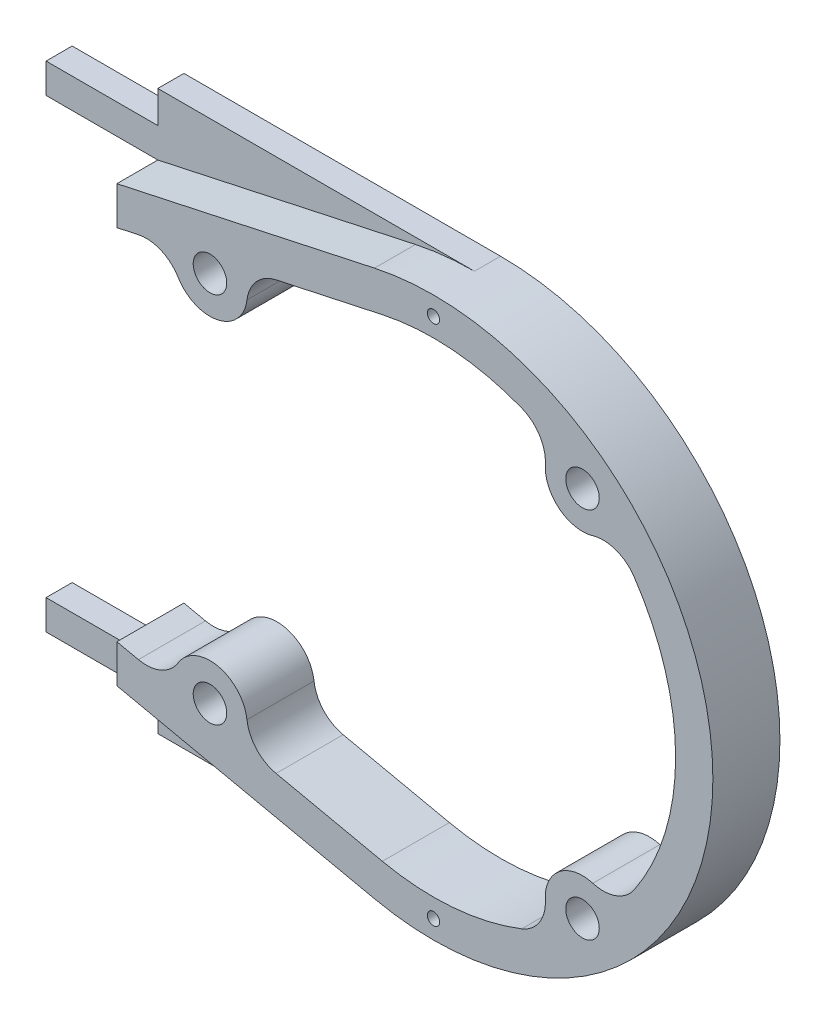
SolidWorks part; units mm, degrees
ref_plane "Front" through (0, 0, 0) normal (0, 0, 1) x (1, 0, 0)
ref_plane "Top" through (0, 0, 0) normal (0, 1, 0) x (1, 0, 0)
ref_plane "Right" through (0, 0, 0) normal (1, 0, 0) x (0, 0, -1)
sketch "Sketch1" plane through (47.5, -47.5, 0) normal (0, 0, 1) x (0, -1, 0)
  line L0 (-15.5701, -207.5) -> (1.8871, -126.7029)
  line L1 (-111.0339, -61.2273) -> (-104.8697, -89.757)
  line L2 (-79.4299, -207.5) -> (-15.5701, -207.5)
  line L3 (-96.8871, -126.7029) -> (-79.4299, -207.5)
  line L4 (-111.0339, -61.2273) -> (-79.4299, -207.5) construction
  line L5 (9.8697, -89.757) -> (16.0339, -61.2273)
  line L6 (-120.8084, -63.3392) -> (-89.2043, -209.6119)
  line L7 (-79.4299, -217.5) -> (-15.5701, -217.5)
  line L8 (-5.7957, -209.6119) -> (25.8084, -63.3392)
  line L9 (-15.5701, -207.5) -> (16.0339, -61.2273) construction
  line L10 (-97.5, -107.5) -> (-97.5, -7.5) construction
  line L11 (2.5, -107.5) -> (2.5, -7.5) construction
  line L12 (2.5, -7.5) -> (-97.5, -7.5) construction
  line L13 (-47.5, -47.5) -> (-47.5, -323.5722) construction
  line L14 (43.5196, -47.5) -> (-142.3518, -47.5) construction
  arc A0 (-108.033, -23.8196) -> (-111.0339, -61.2273) centre (-47.5, -47.5) ccw
  arc A1 (16.0339, -61.2273) -> (-111.0339, -61.2273) centre (-47.5, -47.5) ccw construction
  arc A2 (-11.1095, 6.3584) -> (-83.8905, 6.3584) centre (-47.5, -47.5) ccw
  arc A3 (16.0339, -61.2273) -> (13.033, -23.8196) centre (-47.5, -47.5) ccw
  arc A4 (-79.4299, -207.5) -> (-79.4299, -207.5) centre (-79.4299, -207.5) ccw
  arc A5 (-15.5701, -207.5) -> (-15.5701, -207.5) centre (-15.5701, -207.5) ccw
  arc A6 (-89.2043, -209.6119) -> (-79.4299, -217.5) centre (-79.4299, -207.5) ccw
  arc A7 (-15.5701, -217.5) -> (-5.7957, -209.6119) centre (-15.5701, -207.5) ccw
  arc A8 (25.8084, -63.3392) -> (-120.8084, -63.3392) centre (-47.5, -47.5) ccw
  arc A9 (-92.3063, -116.0455) -> (-96.2976, -97.5725) centre (-97.5, -107.5) ccw
  circle A10 centre (-97.5, -107.5) radius 4.5
  circle A11 centre (2.5, -107.5) radius 4.5
  circle A12 centre (2.5, -7.5) radius 4.5
  circle A13 centre (-97.5, -7.5) radius 4.5
  arc A14 (-98.1101, -17.4814) -> (-87.896, -4.7138) centre (-97.5, -7.5) ccw
  arc A15 (-7.104, -4.7138) -> (3.1101, -17.4814) centre (2.5, -7.5) ccw
  arc A16 (1.2976, -97.5725) -> (-2.6937, -116.0455) centre (2.5, -107.5) ccw
  arc A17 (1.8871, -126.7029) -> (-2.6937, -116.0455) centre (-7.8873, -124.591) ccw
  arc A18 (9.8697, -89.757) -> (1.2976, -97.5725) centre (0.0953, -87.6451) cw
  arc A19 (3.1101, -17.4814) -> (13.033, -23.8196) centre (3.7202, -27.4627) cw
  arc A20 (-7.104, -4.7138) -> (-11.1095, 6.3584) centre (-16.708, -1.9275) ccw
  arc A21 (-87.896, -4.7138) -> (-83.8905, 6.3584) centre (-78.292, -1.9275) cw
  arc A22 (-98.1101, -17.4814) -> (-108.033, -23.8196) centre (-98.7202, -27.4627) ccw
  arc A23 (-104.8697, -89.757) -> (-96.2976, -97.5725) centre (-95.0953, -87.6451) ccw
  arc A24 (-92.3063, -116.0455) -> (-96.8871, -126.7029) centre (-87.1127, -124.591) ccw
  circle A26 centre (-117.5, -47.5) radius 1.65
  circle A27 centre (22.5, -47.5) radius 1.65
  point P22 (-47.5, -47.5)
  dimension "D2" = 75
  dimension "D7" = 9
  dimension "D8" = 9
  dimension "D9" = 9
  dimension "D10" = 9
  dimension "D16" = 10
  dimension "D17" = 10
  dimension "D18" = 10
  dimension "D19" = 10
  dimension "D20" = 10
  dimension "D21" = 3.3
  dimension "D22" = 3.3
  dimension "D24" = 70
  dimension "D3" = 50
  dimension "D4" = 50
  dimension "D5" = 40
  dimension "D6" = 100
  dimension "D11" = 100
  dimension "D12" = 160
  dimension "D13" = 63.8597
  dimension "D14" = 12.192
  dimension "D15" = 12.192
  dimension "D23" = 70
  dimension "D1" = 10
extrude "Boss-Extrude1" add sketch "Sketch1" along normal blind 18
sketch "Sketch3" plane through (0, 0, 0) normal (0, 0, -1) x (-1, 0, 0)
  line L0 (0, 0) -> (261.4966, 0) construction
  line L2 (265, 75) -> (0, 75)
  line L3 (275, 65) -> (275, -65)
  line L4 (265, -75) -> (0, -75)
  line L5 (0, 75) -> (0, -75)
  line L6 (275, 75) -> (0, -75) construction
  line L7 (275, -75) -> (0, 75) construction
  line L9 (170, 31.9299) -> (170, -31.9299) construction
  arc A0 (265, -75) -> (275, -65) centre (265, -65) ccw
  arc A1 (275, 65) -> (265, 75) centre (265, 65) ccw
  point P3 (137.5, 0)
  point P18 (0, 70)
  dimension "D3" = 10
  dimension "D1" = 75
  dimension "D2" = 105
extrude "Boss-Extrude2" add sketch "Sketch3" against normal blind 7
sketch "Sketch4" plane through (0, 0, 7) normal (0, 0, 1) x (1, 0, 0)
  line L0 (0, 0) -> (-275, 0) construction
  line L1 (-275, -65) -> (-275, 65) construction
  line L2 (0, -11) -> (-275, -11) construction
  line L3 (0, 66.4999) -> (0, -66.4999) construction
  line L4 (0, 11) -> (-275, 11) construction
  line L5 (0, -33) -> (-275, -33) construction
  line L6 (0, 33) -> (-275, 33) construction
  line L7 (-88.9755, -55) -> (-260.4482, -55) construction
  line L8 (0, 55) -> (-275, 55) construction
  line L9 (0, 66.4999) -> (0, -66.4999) construction
  line L10 (-266, 75) -> (-266, -75) construction
  line L11 (-265, 75) -> (0, 75) construction
  line L12 (0, -75) -> (-265, -75) construction
  line L13 (-183, 75) -> (-183, -75) construction
  circle A0 centre (-266, 55) radius 1.2
  circle A1 centre (-266, 33) radius 1.2
  circle A2 centre (-266, 11) radius 1.2
  circle A3 centre (-266, -11) radius 1.2
  circle A4 centre (-266, -33) radius 1.2
  circle A5 centre (-266, -55) radius 1.2
  circle A6 centre (-183, 55) radius 1.2
  circle A7 centre (-183, 33) radius 1.2
  circle A8 centre (-183, 11) radius 1.2
  circle A9 centre (-183, -11) radius 1.2
  circle A10 centre (-183, -33) radius 1.2
  circle A11 centre (-183, -55) radius 1.2
  dimension "D8" = 2.4
  dimension "D9" = 2.4
  dimension "D10" = 2.4
  dimension "D11" = 2.4
  dimension "D12" = 2.4
  dimension "D13" = 2.4
  dimension "D14" = 83
  dimension "D15" = 2.4
  dimension "D16" = 2.4
  dimension "D17" = 2.4
  dimension "D18" = 2.4
  dimension "D19" = 2.4
  dimension "D20" = 2.4
  dimension "D1" = 11
  dimension "D2" = 11
  dimension "D3" = 22
  dimension "D4" = 22
  dimension "D5" = 22
  dimension "D6" = 22
  dimension "D7" = 9
extrude "Cut-Extrude1" cut sketch "Sketch4" against normal through all
sketch "Sketch5" plane through (0, 0, 7) normal (0, 0, 1) x (1, 0, 0)
  line L6 (-42.257, -57.3697) -> (-13.7273, -63.5339)
  line L7 (0, -65) -> (0, 65)
  line L8 (-13.7273, 63.5339) -> (-42.257, 57.3697)
  line L9 (-79.2029, 49.3871) -> (-160, 31.9299)
  line L10 (-160, 31.9299) -> (-160, -31.9299)
  line L11 (-160, -31.9299) -> (-79.2029, -49.3871)
  line L12 (-42.257, -57.3697) -> (-13.7273, -63.5339)
  line L14 (-13.7273, 63.5339) -> (-42.257, 57.3697)
  line L15 (-79.2029, 49.3871) -> (-160, 31.9299)
  line L16 (-160, 31.9299) -> (-160, -31.9299)
  line L17 (-160, -31.9299) -> (-79.2029, -49.3871)
  line L18 (0, -65) -> (0, 65)
  circle A0 centre (-60, 50) radius 4.5 construction
  circle A1 centre (-60, -50) radius 4.5 construction
  circle A2 centre (-60, 50) radius 4.5
  circle A3 centre (-60, -50) radius 4.5
  arc A6 (-50.0725, -48.7976) -> (-42.257, -57.3697) centre (-40.1451, -47.5953) ccw
  arc A7 (-42.257, 57.3697) -> (-50.0725, 48.7976) centre (-40.1451, 47.5953) ccw
  arc A8 (-68.5455, 44.8063) -> (-50.0725, 48.7976) centre (-60, 50) ccw
  arc A9 (-68.5455, 44.8063) -> (-79.2029, 49.3871) centre (-77.091, 39.6127) ccw
  arc A10 (-79.2029, -49.3871) -> (-68.5455, -44.8063) centre (-77.091, -39.6127) ccw
  arc A11 (-50.0725, -48.7976) -> (-68.5455, -44.8063) centre (-60, -50) ccw
  arc A12 (-50.0725, -48.7976) -> (-42.257, -57.3697) centre (-40.1451, -47.5953) ccw
  arc A13 (-42.257, 57.3697) -> (-50.0725, 48.7976) centre (-40.1451, 47.5953) ccw
  arc A14 (-68.5455, 44.8063) -> (-50.0725, 48.7976) centre (-60, 50) ccw
  arc A15 (-68.5455, 44.8063) -> (-79.2029, 49.3871) centre (-77.091, 39.6127) ccw
  arc A16 (-79.2029, -49.3871) -> (-68.5455, -44.8063) centre (-77.091, -39.6127) ccw
  arc A17 (-50.0725, -48.7976) -> (-68.5455, -44.8063) centre (-60, -50) ccw
  arc A24 (-13.7273, -63.5339) -> (0, -65) centre (0, 0) ccw
  arc A25 (-13.7273, -63.5339) -> (0, -65) centre (0, 0) ccw
  arc A26 (0, 65) -> (-13.7273, 63.5339) centre (0, 0) ccw
  arc A27 (0, 65) -> (-13.7273, 63.5339) centre (0, 0) ccw
  dimension "D1" = 0
extrude "Cut-Extrude2" cut sketch "Sketch5" against normal through all
sketch "Sketch6" plane through (0, 0, 7) normal (0, 0, 1) x (1, 0, 0)
  line L0 (0, -75) -> (-265, -75) construction
  line L1 (-222.5, 75) -> (-222.5, -75) construction
  line L2 (-275, 0) -> (-170, 0) construction
  line L4 (-265, 71) -> (-180, 71)
  line L5 (-271, 65) -> (-271, -65)
  line L6 (-162.1119, 41.7043) -> (-15.8392, 73.3084)
  line L7 (0, 75) -> (-265, 75)
  line L8 (-275, 65) -> (-275, -65)
  line L9 (-265, -75) -> (0, -75)
  line L10 (-15.8392, -73.3084) -> (-162.1119, -41.7043)
  line L11 (-170, -31.9299) -> (-170, 31.9299)
  line L13 (-180, 75) -> (-265, 75)
  line L14 (-275, 65) -> (-275, -65)
  line L15 (-265, -75) -> (-180, -75)
  line L17 (-170, -65) -> (-170, 65)
  line L18 (-265, -71) -> (-180, -71)
  line L19 (-174, 65) -> (-174, -65)
  line L20 (-271, 71) -> (-174, -71) construction
  line L21 (-271, -71) -> (-174, 71) construction
  arc A0 (-180, -75) -> (-170, -65) centre (-180, -65) ccw
  arc A1 (-170, 65) -> (-180, 75) centre (-180, 65) ccw
  arc A2 (-180, 71) -> (-174, 65) centre (-180, 65) cw
  arc A3 (-174, -65) -> (-180, -71) centre (-180, -65) cw
  arc A4 (-162.1119, 41.7043) -> (-170, 31.9299) centre (-160, 31.9299) ccw
  arc A5 (-265, 75) -> (-275, 65) centre (-265, 65) ccw
  arc A6 (-275, -65) -> (-265, -75) centre (-265, -65) ccw
  arc A7 (-170, -31.9299) -> (-162.1119, -41.7043) centre (-160, -31.9299) ccw
  arc A9 (-265, 75) -> (-275, 65) centre (-265, 65) ccw
  arc A10 (-275, -65) -> (-265, -75) centre (-265, -65) ccw
  arc A12 (-265, -71) -> (-271, -65) centre (-265, -65) cw
  arc A13 (-265, 71) -> (-271, 65) centre (-265, 65) ccw
  arc A20 (-15.8392, -73.3084) -> (0, -75) centre (0, 0) ccw
  arc A22 (0, 75) -> (-15.8392, 73.3084) centre (0, 0) ccw
  point P21 (-170, -75)
  point P27 (-222.5, 0)
  dimension "D2" = 10
  dimension "D7" = 6
  dimension "D3" = 4
  dimension "D4" = 4
  dimension "D5" = 4
  dimension "D6" = 4
  dimension "D1" = 0
extrude "Boss-Extrude3" add sketch "Sketch6" along normal blind 92
sketch "Sketch7" plane through (-170, 0, 0) normal (1, 0, 0) x (0, 0, -1)
  line L0 (-18, 31.9299) -> (-18, -31.9299) construction
  line L1 (0, 0) -> (-140.0795, 0) construction
  circle A0 centre (-78, 48) radius 15
  circle A1 centre (-78, -48) radius 15
  dimension "D1" = 30
  dimension "D3" = 48
  dimension "D2" = 60
  dimension "D4" = 48
extrude "Cut-Extrude3" cut sketch "Sketch7" against normal up to next
sketch "Sketch8" plane through (0, -75, 0) normal (0, -1, 0) x (1, 0, 0)
  line L1 (-265, 99) -> (-180, 99) construction
  line L2 (-201.547, 79) -> (-275, 79)
  line L3 (-275, 99) -> (-275, 0) construction
  line L4 (-275, 79) -> (-275, 99)
  line L5 (-275, 99) -> (-190, 99)
  line L8 (-201.547, 79) -> (-190, 99)
  line L9 (-170, 99) -> (-170, 7) construction
  dimension "D1" = 60
  dimension "D2" = 20
  dimension "D3" = 20
  dimension "D4" = 85
extrude "Cut-Extrude4" cut sketch "Sketch8" against normal through all
sketch "Sketch10" plane through (0, 0, 0) normal (0, 1, 0) x (1, 0, 0)
  line L0 (-257, -64) -> (-257, -19) construction
  line L1 (-259.5, -64) -> (-259.5, -19)
  line L2 (-254.5, -64) -> (-254.5, -19)
  line L3 (-265, -79) -> (-265, 0) construction
  line L4 (-265, -79) -> (-201.547, -79) construction
  line L5 (-244, -64) -> (-244, -19) construction
  line L6 (-246.5, -64) -> (-246.5, -19)
  line L7 (-241.5, -64) -> (-241.5, -19)
  line L8 (-231, -64) -> (-231, -19) construction
  line L9 (-233.5, -64) -> (-233.5, -19)
  line L10 (-228.5, -64) -> (-228.5, -19)
  line L11 (-218, -64) -> (-218, -19) construction
  line L12 (-220.5, -64) -> (-220.5, -19)
  line L13 (-215.5, -64) -> (-215.5, -19)
  line L14 (-205, -64) -> (-205, -19) construction
  line L15 (-207.5, -64) -> (-207.5, -19)
  line L16 (-202.5, -64) -> (-202.5, -19)
  line L17 (-192, -64) -> (-192, -19) construction
  line L18 (-194.5, -64) -> (-194.5, -19)
  line L19 (-189.5, -64) -> (-189.5, -19)
  arc A0 (-259.5, -64) -> (-254.5, -64) centre (-257, -64) ccw
  arc A1 (-254.5, -19) -> (-259.5, -19) centre (-257, -19) ccw
  arc A2 (-246.5, -64) -> (-241.5, -64) centre (-244, -64) ccw
  arc A3 (-241.5, -19) -> (-246.5, -19) centre (-244, -19) ccw
  arc A4 (-233.5, -64) -> (-228.5, -64) centre (-231, -64) ccw
  arc A5 (-228.5, -19) -> (-233.5, -19) centre (-231, -19) ccw
  arc A6 (-220.5, -64) -> (-215.5, -64) centre (-218, -64) ccw
  arc A7 (-215.5, -19) -> (-220.5, -19) centre (-218, -19) ccw
  arc A8 (-207.5, -64) -> (-202.5, -64) centre (-205, -64) ccw
  arc A9 (-202.5, -19) -> (-207.5, -19) centre (-205, -19) ccw
  arc A10 (-194.5, -64) -> (-189.5, -64) centre (-192, -64) ccw
  arc A11 (-189.5, -19) -> (-194.5, -19) centre (-192, -19) ccw
  point P2 (-257, -41.5)
  point P15 (-244, -41.5)
  point P22 (-231, -41.5)
  point P29 (-218, -41.5)
  point P36 (-205, -41.5)
  point P43 (-192, -41.5)
  dimension "D4" = 15
  dimension "D1" = 45
  dimension "D2" = 8
  dimension "D3" = 5
  dimension "D5" = 6
extrude "Cut-Extrude6" cut sketch "Sketch10" against normal through all both and the other way through all
sketch "Sketch11" plane through (0, 0, 18) normal (0, 0, 1) x (1, 0, 0)
  line L0 (-162.1119, 41.7043) -> (-170, 41.7043)
  line L1 (-170, 31.9299) -> (-170, 65) construction
  line L2 (-170, 41.7043) -> (-170, 31.9299)
  line L4 (0, 0) -> (-275, 0) construction
  line L6 (-275, 65) -> (-275, -65) construction
  line L7 (-170, -41.7043) -> (-170, -31.9299)
  line L8 (-162.1119, -41.7043) -> (-170, -41.7043)
  arc A0 (-162.1119, 41.7043) -> (-170, 31.9299) centre (-160, 31.9299) ccw construction
  arc A1 (-162.1119, 41.7043) -> (-170, 31.9299) centre (-160, 31.9299) ccw
  arc A2 (-162.1119, -41.7043) -> (-170, -31.9299) centre (-160, -31.9299) cw
extrude "Boss-Extrude4" add sketch "Sketch11" against normal up to surface (11 mm away) up to face at (-116.2752, -60.9714, 7)
fillet "Fillet1" radius 20 3 edges at (-172.9289, 72.0711, 7) (-172.9289, -72.0711, 7) (-170, -53.3522, 7)
sketch "Sketch12" plane through (-170, 0, 0) normal (1, 0, 0) x (0, 0, -1)
  line L0 (-18, 75) -> (-18, -75) construction
  line L1 (-29.3941, 41.7043) -> (-18, 41.7043)
  line L2 (-29.3941, 41.7043) -> (-29.3941, -41.7043)
  line L3 (-29.3941, -41.7043) -> (-18, -41.7043)
  line L4 (-18, 41.7043) -> (-18, -41.7043)
  line L5 (-18, 41.7043) -> (-11.0845, 41.7043) construction
  line L6 (-18, -41.7043) -> (-11.0845, -41.7043) construction
extrude "Cut-Extrude7" cut sketch "Sketch12" along normal blind 9.5
sketch "Sketch13" plane through (0, 0, 79) normal (0, 0, 1) x (1, 0, 0)
  line L0 (-271, 61) -> (-261, 71)
  line L1 (-271, -65) -> (-271, 65) construction
  line L2 (-180, 71) -> (-265, 71) construction
  line L3 (-271, 65) -> (-271, -65) construction
  line L4 (-275, 65) -> (-275, -65) construction
  line L5 (-265, 71) -> (-201.547, 71) construction
  line L6 (-271, 61) -> (-271, 65)
  line L7 (-265, 71) -> (-261, 71)
  line L8 (-265, -71) -> (-180, -71) construction
  line L16 (0, 0) -> (-275, 0) construction
  line L20 (-271, -61) -> (-261, -71)
  line L21 (-261, -71) -> (-265, -71)
  line L22 (-271, -61) -> (-271, -65)
  arc A1 (-265, 71) -> (-271, 65) centre (-265, 65) ccw construction
  arc A2 (-265, 71) -> (-271, 65) centre (-265, 65) ccw
  arc A3 (-271, -65) -> (-265, -71) centre (-265, -65) ccw construction
  arc A4 (-271, -65) -> (-265, -71) centre (-265, -65) ccw
  dimension "D2" = 45
  dimension "D3" = 14
  dimension "D7" = 45
  dimension "D8" = 14
extrude "Boss-Extrude5" add sketch "Sketch13" against normal blind 10
sketch "Sketch14" plane through (0, 0, 79) normal (0, 0, 1) x (1, 0, 0)
  line L1 (-275, 65) -> (-275, -65) construction
  line L2 (-265, 75) -> (-201.547, 75) construction
  line L5 (-265, -75) -> (-201.547, -75) construction
  circle A0 centre (-267.5, 67.5) radius 1.25
  circle A3 centre (-267.5, -67.5) radius 1.25
  dimension "D1" = 2.5
  dimension "D2" = 7.5
  dimension "D3" = 2.5
  dimension "D6" = 7.5
  dimension "7" = 7.5
  dimension "D8" = 7.5
extrude "Cut-Extrude8" cut sketch "Sketch14" against normal blind 6
chamfer "Chamfer2" distance 3.9 angle 45 2 edges at (-266, -66, 69) (-266, 66, 69)
sketch "Sketch15" plane through (0, -71, 0) normal (0, 1, 0) x (1, 0, 0)
  line L0 (-180, -99) -> (-190, -99) construction
  line L1 (-170, -99) -> (-170, -27) construction
  circle A0 centre (-184, -94) radius 1.75
  point P0 (-184, -94)
  dimension "D3" = 3.5
  dimension "D1" = 5
  dimension "D2" = 14
extrude "Cut-Extrude9" cut sketch "Sketch15" against normal through all and the other way through all
sketch "Sketch16" plane through (0, -75, 0) normal (0, -1, 0) x (1, 0, 0)
  circle A0 centre (-184, 94) radius 3.15
  dimension "D1" = 6.3
extrude "Cut-Extrude10" cut sketch "Sketch16" against normal blind 1.5
sketch "Sketch17" plane through (0, 75, 0) normal (0, 1, 0) x (1, 0, 0)
  circle A0 centre (-184, -94) radius 3.15
  dimension "D1" = 6.3
extrude "Cut-Extrude11" cut sketch "Sketch17" against normal blind 1.5
fillet "Fillet2" radius 3 2 edges at (-190, 73, 99) (-190, -73, 99)
sketch "Sketch18" plane through (-170, 0, 0) normal (1, 0, 0) x (0, 0, -1)
  line L0 (0, 0) -> (-99, 0) construction
  line L1 (-99, -65) -> (-99, 65) construction
  line L2 (-18, 75) -> (-18, -75) construction
  line L3 (-40.9, 20) -> (-30.9, 20)
  line L4 (-40.9, 20) -> (-40.9, -20)
  line L5 (-40.9, -20) -> (-30.9, -20)
  line L6 (-30.9, 20) -> (-30.9, -20)
  line L7 (-40.9, 20) -> (-30.9, -20) construction
  line L8 (-40.9, -20) -> (-30.9, 20) construction
  point P5 (-35.9, 0)
  dimension "D1" = 12.9
  dimension "D2" = 40
  dimension "D3" = 10
extrude "Boss-Extrude6" add sketch "Sketch18" along normal blind 5
chamfer "Chamfer3" distance 4 angle 45 1 edges at (-165, 0, 40.9)
sketch "Sketch19" plane through (-275, 0, 0) normal (-1, 0, 0) x (0, 0, 1)
  line L0 (79, 65) -> (0, 65) construction
  line L3 (79, 65) -> (79, -65) construction
  circle A0 centre (33.5, 20) radius 19
  dimension "D1" = 38
  dimension "D2" = 45
  dimension "D3" = 45.5
extrude "Cut-Extrude12" cut sketch "Sketch19" against normal up to next
sketch "Sketch20" plane through (-275, 0, 0) normal (-1, 0, 0) x (0, 0, 1)
  line L0 (79, 65) -> (79, -65) construction
  line L1 (79, 75) -> (0, 75) construction
  circle A0 centre (8.75, -31) radius 1.25
  circle A1 centre (58.75, -31) radius 1.25
  circle A2 centre (8.75, 39) radius 1.25
  circle A3 centre (58.75, 39) radius 1.25
  point P0 (8.75, 39)
  point P1 (58.75, 39)
  point P3 (58.75, -31)
  point P5 (8.75, -31)
  dimension "D5" = 2.5
  dimension "D6" = 2.5
  dimension "D7" = 2.5
  dimension "D8" = 2.5
  dimension "D1" = 50
  dimension "D2" = 20.25
  dimension "D3" = 70
  dimension "D4" = 36
extrude "Cut-Extrude13" cut sketch "Sketch20" against normal up to next
sketch "Sketch21" plane through (-275, 0, 0) normal (-1, 0, 0) x (0, 0, 1)
  line L0 (0, -65) -> (0, 65) construction
  line L1 (79, 75) -> (0, 75) construction
  circle A0 centre (32, -10) radius 6
  dimension "D1" = 12
  dimension "D2" = 32
  dimension "D3" = 85
extrude "Cut-Extrude14" cut sketch "Sketch21" against normal up to next
sketch "Sketch22" plane through (0, 0, 0) normal (0, 0, -1) x (-1, 0, 0)
  line L0 (151.7157, 75) -> (0, 75) construction
  line L1 (85, 75) -> (-82.1289, 75)
  line L2 (85, 75) -> (85, 66.3653)
  line L3 (85, -75) -> (-82.1289, -75)
  line L4 (-82.1289, 75) -> (-82.1289, -75)
  line L5 (0, -75) -> (151.7157, -75) construction
  line L6 (150, 44.3213) -> (15.8392, 73.3084) construction
  line L7 (85, 58.3653) -> (115, 58.3653)
  line L9 (85, 66.3653) -> (115, 66.3653)
  line L10 (115, 58.3653) -> (115, 66.3653)
  line L11 (162.1119, -41.7043) -> (15.8392, -73.3084) construction
  line L12 (85, -58.3653) -> (115, -58.3653)
  line L14 (85, -66.3653) -> (115, -66.3653)
  line L15 (115, -58.3653) -> (115, -66.3653)
  line L16 (85, 58.3653) -> (85, -58.3653)
  line L17 (85, -66.3653) -> (85, -75)
  arc A0 (15.8392, 73.3084) -> (15.8392, -73.3084) centre (0, 0) ccw construction
  point P24 (-75, 0)
  dimension "D1" = 190
  dimension "D2" = 8
  dimension "D3" = 8
  dimension "D4" = 190
extrude "Cut-Extrude15" cut sketch "Sketch22" against normal through all flip side to cut
